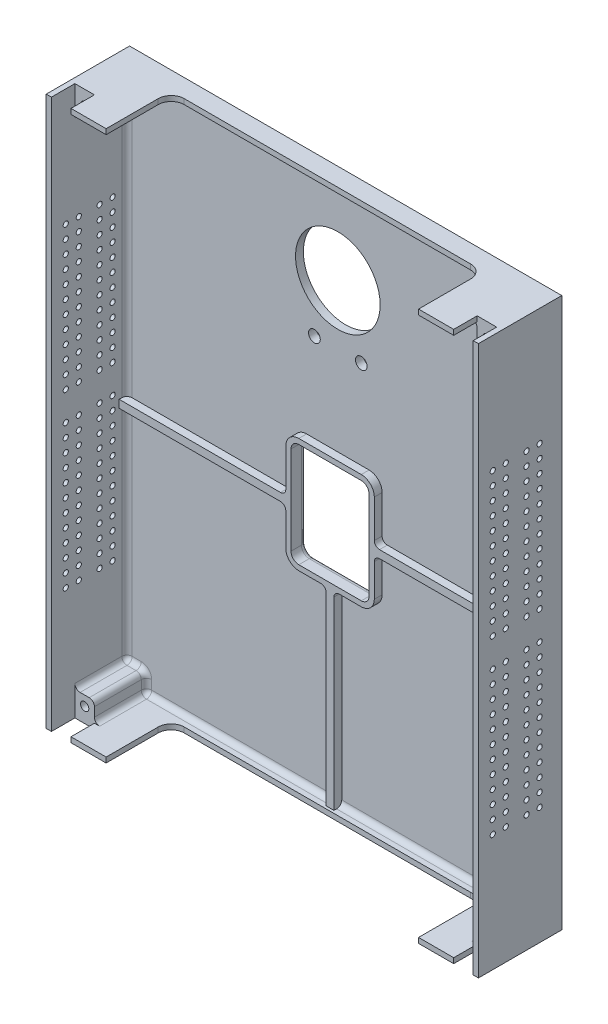
SolidWorks part; units mm, degrees
ref_plane "Front Plane" through (0, 0, 0) normal (0, 0, 1) x (1, 0, 0)
ref_plane "Top Plane" through (0, 0, 0) normal (0, 1, 0) x (1, 0, 0)
ref_plane "Right Plane" through (0, 0, 0) normal (1, 0, 0) x (0, 0, -1)
ref_plane "Plane1" through (0, 0, -1) normal (0, 0, 1) x (1, 0, 0)
sketch "Sketch5" plane through (0, 0, -1) normal (0, 0, 1) x (1, 0, 0)
  line L0 (100, 83.2573) -> (100, -169.2647) construction
  line L2 (17, 83.2573) -> (17, -127.7573)
  line L3 (17, -127.7573) -> (183, -127.7573)
  line L4 (183, 83.2573) -> (183, -127.7573)
  line L5 (17, 83.2573) -> (183, 83.2573)
  circle A0 centre (100, 48.2573) radius 16.25
  point P17 (45, 83.2573)
  dimension "D1" = 166
  dimension "D2" = 83
extrude "Boss-Extrude5" add sketch "Sketch5" along normal blind 3
sketch "Sketch6" plane through (0, 0, 2) normal (0, 0, 1) x (1, 0, 0)
  line L0 (116.25, 48.2573) -> (83.75, 48.2573) construction
  line L2 (86, 35.0451) -> (86, 18.2573)
  line L3 (86, 18.2573) -> (114, 18.2573)
  line L4 (114, 35.0451) -> (114, 18.2573)
  line L5 (100, 48.2573) -> (100, 52.872) construction
  circle A1 centre (100, 48.2573) radius 16.25
  arc A2 (114, 35.0451) -> (86, 35.0451) centre (100, 48.2573) ccw
  circle A6 centre (100, 48.2573) radius 16.25 construction
extrude "Boss-Extrude6" add sketch "Sketch6" along normal blind 3
sketch "Sketch7" plane through (0, 0, 5) normal (0, 0, 1) x (1, 0, 0)
  line L0 (112.75, 33.8351) -> (112.75, 48.2573)
  line L2 (87.25, 48.2573) -> (87.25, 33.8351)
  line L3 (100, 64.5073) -> (100, 48.2573) construction
  line L4 (100, 48.2573) -> (116.25, 48.2573) construction
  arc A8 (112.75, 33.8351) -> (87.25, 33.8351) centre (100, 48.2573) ccw
  circle A9 centre (100, 48.2573) radius 19.25 construction
  circle A10 centre (100, 48.2573) radius 16.25 construction
  circle A12 centre (100, 48.2573) radius 12.75
  arc A13 (112.75, 48.2573) -> (87.25, 48.2573) centre (100, 48.2573) ccw
  dimension "D1" = 1
extrude "Boss-Extrude7" add sketch "Sketch7" along normal blind 4
sketch "Sketch8" plane through (0, 0, 2) normal (0, 0, 1) x (1, 0, 0)
  line L4 (17, -127.7573) -> (183, -127.7573)
  line L5 (183, -127.7573) -> (183, 83.2573)
  line L6 (183, 83.2573) -> (17, 83.2573)
  line L7 (17, 83.2573) -> (17, -127.7573)
  line L8 (17, -127.7573) -> (183, -127.7573)
  line L9 (183, -127.7573) -> (183, 83.2573)
  line L10 (183, 83.2573) -> (17, 83.2573)
  line L11 (17, 83.2573) -> (17, -127.7573)
  line L12 (19, -125.7573) -> (181, -125.7573)
  line L13 (181, -125.7573) -> (181, 81.2573)
  line L14 (181, 81.2573) -> (19, 81.2573)
  line L15 (19, 81.2573) -> (19, -125.7573)
  dimension "D1" = 0
  dimension "D2" = 2
extrude "Boss-Extrude8" add sketch "Sketch8" along normal blind 29
fillet "Fillet2" radius 3 4 edges at (114, 18.2573, 3.5) (114, 35.0451, 3.5) (86, 18.2573, 3.5) (86, 35.0451, 3.5)
sketch "Sketch12" plane through (183, 0, 0) normal (1, 0, 0) x (0, 0, -1)
  circle A0 centre (-12.5, -16.7427) radius 1
  circle A1 centre (-7.5, -16.7427) radius 1
  circle A2 centre (-7.5, -11.7427) radius 1
  circle A3 centre (-7.5, -6.7427) radius 1
  circle A4 centre (-7.5, -1.7427) radius 1
  circle A5 centre (-7.5, 3.2573) radius 1
  circle A6 centre (-7.5, 8.2573) radius 1
  circle A7 centre (-7.5, 13.2573) radius 1
  circle A8 centre (-7.5, 18.2573) radius 1
  circle A9 centre (-7.5, 23.2573) radius 1
  circle A10 centre (-7.5, 28.2573) radius 1
  circle A11 centre (-7.5, 33.2573) radius 1
  circle A12 centre (-7.5, 38.2573) radius 1
  circle A13 centre (-12.5, -11.7427) radius 1
  circle A14 centre (-12.5, -6.7427) radius 1
  circle A15 centre (-12.5, -1.7427) radius 1
  circle A16 centre (-12.5, 3.2573) radius 1
  circle A17 centre (-12.5, 8.2573) radius 1
  circle A18 centre (-12.5, 13.2573) radius 1
  circle A19 centre (-12.5, 18.2573) radius 1
  circle A20 centre (-12.5, 23.2573) radius 1
  circle A21 centre (-12.5, 28.2573) radius 1
  circle A22 centre (-12.5, 33.2573) radius 1
  circle A23 centre (-12.5, 38.2573) radius 1
  circle A24 centre (-12.5, -82.7573) radius 1
  circle A25 centre (-12.5, -77.7573) radius 1
  circle A26 centre (-12.5, -72.7573) radius 1
  circle A27 centre (-12.5, -67.7573) radius 1
  circle A28 centre (-12.5, -62.7573) radius 1
  circle A29 centre (-12.5, -57.7573) radius 1
  circle A30 centre (-12.5, -52.7573) radius 1
  circle A31 centre (-12.5, -47.7573) radius 1
  circle A32 centre (-12.5, -42.7573) radius 1
  circle A33 centre (-12.5, -37.7573) radius 1
  circle A34 centre (-12.5, -32.7573) radius 1
  circle A35 centre (-7.5, -82.7573) radius 1
  circle A36 centre (-7.5, -77.7573) radius 1
  circle A37 centre (-7.5, -72.7573) radius 1
  circle A38 centre (-7.5, -67.7573) radius 1
  circle A39 centre (-7.5, -62.7573) radius 1
  circle A40 centre (-7.5, -57.7573) radius 1
  circle A41 centre (-7.5, -52.7573) radius 1
  circle A42 centre (-7.5, -47.7573) radius 1
  circle A43 centre (-7.5, -42.7573) radius 1
  circle A44 centre (-7.5, -37.7573) radius 1
  circle A45 centre (-7.5, -32.7573) radius 1
  circle A46 centre (-7.5, -27.7573) radius 1
  circle A47 centre (-12.5, -27.7573) radius 1
  circle A48 centre (-20.5, -27.7573) radius 1
  circle A49 centre (-25.5, -27.7573) radius 1
  circle A50 centre (-25.5, -32.7573) radius 1
  circle A51 centre (-25.5, -37.7573) radius 1
  circle A52 centre (-25.5, -42.7573) radius 1
  circle A53 centre (-25.5, -47.7573) radius 1
  circle A54 centre (-25.5, -52.7573) radius 1
  circle A55 centre (-25.5, -57.7573) radius 1
  circle A56 centre (-25.5, -62.7573) radius 1
  circle A57 centre (-25.5, -67.7573) radius 1
  circle A58 centre (-25.5, -72.7573) radius 1
  circle A59 centre (-25.5, -77.7573) radius 1
  circle A60 centre (-25.5, -82.7573) radius 1
  circle A61 centre (-20.5, -32.7573) radius 1
  circle A62 centre (-20.5, -37.7573) radius 1
  circle A63 centre (-20.5, -42.7573) radius 1
  circle A64 centre (-20.5, -47.7573) radius 1
  circle A65 centre (-20.5, -52.7573) radius 1
  circle A66 centre (-20.5, -57.7573) radius 1
  circle A67 centre (-20.5, -62.7573) radius 1
  circle A68 centre (-20.5, -67.7573) radius 1
  circle A69 centre (-20.5, -72.7573) radius 1
  circle A70 centre (-20.5, -77.7573) radius 1
  circle A71 centre (-20.5, -82.7573) radius 1
  circle A72 centre (-20.5, 38.2573) radius 1
  circle A73 centre (-20.5, 33.2573) radius 1
  circle A74 centre (-20.5, 28.2573) radius 1
  circle A75 centre (-20.5, 23.2573) radius 1
  circle A76 centre (-20.5, 18.2573) radius 1
  circle A77 centre (-20.5, 13.2573) radius 1
  circle A78 centre (-20.5, 8.2573) radius 1
  circle A79 centre (-20.5, 3.2573) radius 1
  circle A80 centre (-20.5, -1.7427) radius 1
  circle A81 centre (-20.5, -6.7427) radius 1
  circle A82 centre (-20.5, -11.7427) radius 1
  circle A83 centre (-25.5, 38.2573) radius 1
  circle A84 centre (-25.5, 33.2573) radius 1
  circle A85 centre (-25.5, 28.2573) radius 1
  circle A86 centre (-25.5, 23.2573) radius 1
  circle A87 centre (-25.5, 18.2573) radius 1
  circle A88 centre (-25.5, 13.2573) radius 1
  circle A89 centre (-25.5, 8.2573) radius 1
  circle A90 centre (-25.5, 3.2573) radius 1
  circle A91 centre (-25.5, -1.7427) radius 1
  circle A92 centre (-25.5, -6.7427) radius 1
  circle A93 centre (-25.5, -11.7427) radius 1
  circle A94 centre (-25.5, -16.7427) radius 1
  circle A95 centre (-20.5, -16.7427) radius 1
  dimension "D1" = 2
  dimension "D2" = 12
extrude "Cut-Extrude4" cut sketch "Sketch12" against normal up to surface (2 mm away) up to face at (181, -22.25, 16.5)
sketch "Sketch13" plane through (0, 0, -1) normal (0, 0, -1) x (-1, 0, 0)
  line L0 (-183, -30.7808) -> (-100, -30.7808) construction
  line L1 (-183, -127.7573) -> (-183, 83.2573) construction
  line L6 (-100, 83.2573) -> (-100, -30.7808) construction
  line L7 (-183, 83.2573) -> (-17, 83.2573) construction
  line L14 (-85, -47.7808) -> (-85, -13.7808)
  line L15 (-88, -10.7808) -> (-112, -10.7808)
  line L16 (-115, -13.7808) -> (-115, -47.7808)
  line L17 (-112, -50.7808) -> (-88, -50.7808)
  circle A1 centre (-100, -30.7808) radius 9 construction
  arc A15 (-88, -50.7808) -> (-85, -47.7808) centre (-88, -47.7808) ccw
  arc A16 (-85, -13.7808) -> (-88, -10.7808) centre (-88, -13.7808) ccw
  arc A17 (-112, -10.7808) -> (-115, -13.7808) centre (-112, -13.7808) ccw
  arc A18 (-115, -47.7808) -> (-112, -50.7808) centre (-112, -47.7808) ccw
extrude "Cut-Extrude5" cut sketch "Sketch13" against normal blind 3
sketch "Sketch14" plane through (17, 0, 0) normal (-1, 0, 0) x (0, 0, 1)
  circle A1 centre (12.5, -82.7573) radius 1
  circle A2 centre (12.5, -82.7573) radius 1
  circle A3 centre (12.5, -16.7427) radius 1
  circle A4 centre (12.5, -16.7427) radius 1
  circle A5 centre (7.5, 18.2573) radius 1
  circle A6 centre (7.5, 18.2573) radius 1
  circle A7 centre (7.5, 13.2573) radius 1
  circle A8 centre (7.5, 13.2573) radius 1
  circle A9 centre (7.5, 8.2573) radius 1
  circle A10 centre (7.5, 8.2573) radius 1
  circle A11 centre (7.5, 3.2573) radius 1
  circle A12 centre (7.5, 3.2573) radius 1
  circle A13 centre (7.5, -1.7427) radius 1
  circle A14 centre (7.5, -1.7427) radius 1
  circle A15 centre (7.5, -6.7427) radius 1
  circle A16 centre (7.5, -6.7427) radius 1
  circle A17 centre (7.5, -11.7427) radius 1
  circle A18 centre (7.5, -11.7427) radius 1
  circle A19 centre (7.5, -16.7427) radius 1
  circle A20 centre (7.5, -16.7427) radius 1
  circle A21 centre (12.5, 3.2573) radius 1
  circle A22 centre (12.5, 3.2573) radius 1
  circle A23 centre (12.5, -1.7427) radius 1
  circle A24 centre (12.5, -1.7427) radius 1
  circle A25 centre (12.5, -6.7427) radius 1
  circle A26 centre (12.5, -6.7427) radius 1
  circle A27 centre (12.5, -11.7427) radius 1
  circle A28 centre (12.5, -11.7427) radius 1
  circle A29 centre (7.5, 38.2573) radius 1
  circle A30 centre (7.5, 38.2573) radius 1
  circle A31 centre (7.5, 33.2573) radius 1
  circle A32 centre (7.5, 33.2573) radius 1
  circle A33 centre (7.5, 28.2573) radius 1
  circle A34 centre (7.5, 28.2573) radius 1
  circle A35 centre (7.5, 23.2573) radius 1
  circle A36 centre (7.5, 23.2573) radius 1
  circle A37 centre (12.5, -77.7573) radius 1
  circle A38 centre (12.5, -77.7573) radius 1
  circle A39 centre (12.5, 38.2573) radius 1
  circle A40 centre (12.5, 38.2573) radius 1
  circle A41 centre (12.5, 33.2573) radius 1
  circle A42 centre (12.5, 33.2573) radius 1
  circle A43 centre (12.5, 28.2573) radius 1
  circle A44 centre (12.5, 28.2573) radius 1
  circle A45 centre (12.5, 23.2573) radius 1
  circle A46 centre (12.5, 23.2573) radius 1
  circle A47 centre (12.5, 18.2573) radius 1
  circle A48 centre (12.5, 18.2573) radius 1
  circle A49 centre (12.5, 13.2573) radius 1
  circle A50 centre (12.5, 13.2573) radius 1
  circle A51 centre (12.5, 8.2573) radius 1
  circle A52 centre (12.5, 8.2573) radius 1
  circle A53 centre (12.5, -37.7573) radius 1
  circle A54 centre (12.5, -37.7573) radius 1
  circle A55 centre (12.5, -42.7573) radius 1
  circle A56 centre (12.5, -42.7573) radius 1
  circle A57 centre (12.5, -47.7573) radius 1
  circle A58 centre (12.5, -47.7573) radius 1
  circle A59 centre (12.5, -52.7573) radius 1
  circle A60 centre (12.5, -52.7573) radius 1
  circle A61 centre (12.5, -57.7573) radius 1
  circle A62 centre (12.5, -57.7573) radius 1
  circle A63 centre (12.5, -62.7573) radius 1
  circle A64 centre (12.5, -62.7573) radius 1
  circle A65 centre (12.5, -67.7573) radius 1
  circle A66 centre (12.5, -67.7573) radius 1
  circle A67 centre (12.5, -72.7573) radius 1
  circle A68 centre (12.5, -72.7573) radius 1
  circle A69 centre (7.5, -52.7573) radius 1
  circle A70 centre (7.5, -52.7573) radius 1
  circle A71 centre (7.5, -57.7573) radius 1
  circle A72 centre (7.5, -57.7573) radius 1
  circle A73 centre (7.5, -62.7573) radius 1
  circle A74 centre (7.5, -62.7573) radius 1
  circle A75 centre (7.5, -67.7573) radius 1
  circle A76 centre (7.5, -67.7573) radius 1
  circle A77 centre (7.5, -72.7573) radius 1
  circle A78 centre (7.5, -72.7573) radius 1
  circle A79 centre (7.5, -77.7573) radius 1
  circle A80 centre (7.5, -77.7573) radius 1
  circle A81 centre (7.5, -82.7573) radius 1
  circle A82 centre (7.5, -82.7573) radius 1
  circle A83 centre (12.5, -32.7573) radius 1
  circle A84 centre (12.5, -32.7573) radius 1
  circle A85 centre (25.5, -27.7573) radius 1
  circle A86 centre (25.5, -27.7573) radius 1
  circle A87 centre (20.5, -27.7573) radius 1
  circle A88 centre (20.5, -27.7573) radius 1
  circle A89 centre (12.5, -27.7573) radius 1
  circle A90 centre (12.5, -27.7573) radius 1
  circle A91 centre (7.5, -27.7573) radius 1
  circle A92 centre (7.5, -27.7573) radius 1
  circle A93 centre (7.5, -32.7573) radius 1
  circle A94 centre (7.5, -32.7573) radius 1
  circle A95 centre (7.5, -37.7573) radius 1
  circle A96 centre (7.5, -37.7573) radius 1
  circle A97 centre (7.5, -42.7573) radius 1
  circle A98 centre (7.5, -42.7573) radius 1
  circle A99 centre (7.5, -47.7573) radius 1
  circle A100 centre (7.5, -47.7573) radius 1
  circle A101 centre (25.5, -67.7573) radius 1
  circle A102 centre (25.5, -67.7573) radius 1
  circle A103 centre (25.5, -62.7573) radius 1
  circle A104 centre (25.5, -62.7573) radius 1
  circle A105 centre (25.5, -57.7573) radius 1
  circle A106 centre (25.5, -57.7573) radius 1
  circle A107 centre (25.5, -52.7573) radius 1
  circle A108 centre (25.5, -52.7573) radius 1
  circle A109 centre (25.5, -47.7573) radius 1
  circle A110 centre (25.5, -47.7573) radius 1
  circle A111 centre (25.5, -42.7573) radius 1
  circle A112 centre (25.5, -42.7573) radius 1
  circle A113 centre (25.5, -37.7573) radius 1
  circle A114 centre (25.5, -37.7573) radius 1
  circle A115 centre (25.5, -32.7573) radius 1
  circle A116 centre (25.5, -32.7573) radius 1
  circle A117 centre (20.5, -52.7573) radius 1
  circle A118 centre (20.5, -52.7573) radius 1
  circle A119 centre (20.5, -47.7573) radius 1
  circle A120 centre (20.5, -47.7573) radius 1
  circle A121 centre (20.5, -42.7573) radius 1
  circle A122 centre (20.5, -42.7573) radius 1
  circle A123 centre (20.5, -37.7573) radius 1
  circle A124 centre (20.5, -37.7573) radius 1
  circle A125 centre (20.5, -32.7573) radius 1
  circle A126 centre (20.5, -32.7573) radius 1
  circle A127 centre (25.5, -82.7573) radius 1
  circle A128 centre (25.5, -82.7573) radius 1
  circle A129 centre (25.5, -77.7573) radius 1
  circle A130 centre (25.5, -77.7573) radius 1
  circle A131 centre (25.5, -72.7573) radius 1
  circle A132 centre (25.5, -72.7573) radius 1
  circle A133 centre (20.5, 33.2573) radius 1
  circle A134 centre (20.5, 33.2573) radius 1
  circle A135 centre (20.5, 38.2573) radius 1
  circle A136 centre (20.5, 38.2573) radius 1
  circle A137 centre (20.5, -82.7573) radius 1
  circle A138 centre (20.5, -82.7573) radius 1
  circle A139 centre (20.5, -77.7573) radius 1
  circle A140 centre (20.5, -77.7573) radius 1
  circle A141 centre (20.5, -72.7573) radius 1
  circle A142 centre (20.5, -72.7573) radius 1
  circle A143 centre (20.5, -67.7573) radius 1
  circle A144 centre (20.5, -67.7573) radius 1
  circle A145 centre (20.5, -62.7573) radius 1
  circle A146 centre (20.5, -62.7573) radius 1
  circle A147 centre (20.5, -57.7573) radius 1
  circle A148 centre (20.5, -57.7573) radius 1
  circle A149 centre (20.5, -6.7427) radius 1
  circle A150 centre (20.5, -6.7427) radius 1
  circle A151 centre (20.5, -1.7427) radius 1
  circle A152 centre (20.5, -1.7427) radius 1
  circle A153 centre (20.5, 3.2573) radius 1
  circle A154 centre (20.5, 3.2573) radius 1
  circle A155 centre (20.5, 8.2573) radius 1
  circle A156 centre (20.5, 8.2573) radius 1
  circle A157 centre (20.5, 13.2573) radius 1
  circle A158 centre (20.5, 13.2573) radius 1
  circle A159 centre (20.5, 18.2573) radius 1
  circle A160 centre (20.5, 18.2573) radius 1
  circle A161 centre (20.5, 23.2573) radius 1
  circle A162 centre (20.5, 23.2573) radius 1
  circle A163 centre (20.5, 28.2573) radius 1
  circle A164 centre (20.5, 28.2573) radius 1
  circle A165 centre (25.5, 8.2573) radius 1
  circle A166 centre (25.5, 8.2573) radius 1
  circle A167 centre (25.5, 13.2573) radius 1
  circle A168 centre (25.5, 13.2573) radius 1
  circle A169 centre (25.5, 18.2573) radius 1
  circle A170 centre (25.5, 18.2573) radius 1
  circle A171 centre (25.5, 23.2573) radius 1
  circle A172 centre (25.5, 23.2573) radius 1
  circle A173 centre (25.5, 28.2573) radius 1
  circle A174 centre (25.5, 28.2573) radius 1
  circle A175 centre (25.5, 33.2573) radius 1
  circle A176 centre (25.5, 33.2573) radius 1
  circle A177 centre (25.5, 38.2573) radius 1
  circle A178 centre (25.5, 38.2573) radius 1
  circle A179 centre (20.5, -11.7427) radius 1
  circle A180 centre (20.5, -11.7427) radius 1
  circle A181 centre (20.5, -16.7427) radius 1
  circle A182 centre (20.5, -16.7427) radius 1
  circle A183 centre (25.5, -16.7427) radius 1
  circle A184 centre (25.5, -16.7427) radius 1
  circle A185 centre (25.5, -11.7427) radius 1
  circle A186 centre (25.5, -11.7427) radius 1
  circle A187 centre (25.5, -6.7427) radius 1
  circle A188 centre (25.5, -6.7427) radius 1
  circle A189 centre (25.5, -1.7427) radius 1
  circle A190 centre (25.5, -1.7427) radius 1
  circle A191 centre (25.5, 3.2573) radius 1
  circle A192 centre (25.5, 3.2573) radius 1
  dimension "D1" = 0
  dimension "D2" = 0
  dimension "D3" = 0
  dimension "D4" = 0
  dimension "D5" = 0
  dimension "D6" = 0
  dimension "D7" = 0
  dimension "D8" = 0
  dimension "D9" = 0
  dimension "D10" = 0
  dimension "D11" = 0
  dimension "D12" = 0
  dimension "D13" = 0
  dimension "D14" = 0
  dimension "D15" = 0
  dimension "D16" = 0
  dimension "D17" = 0
  dimension "D18" = 0
  dimension "D19" = 0
  dimension "D20" = 0
  dimension "D21" = 0
  dimension "D22" = 0
  dimension "D23" = 0
  dimension "D24" = 0
  dimension "D25" = 0
  dimension "D26" = 0
  dimension "D27" = 0
  dimension "D28" = 0
  dimension "D29" = 0
  dimension "D30" = 0
  dimension "D31" = 0
  dimension "D32" = 0
  dimension "D33" = 0
  dimension "D34" = 0
  dimension "D35" = 0
  dimension "D36" = 0
  dimension "D37" = 0
  dimension "D38" = 0
  dimension "D39" = 0
  dimension "D40" = 0
  dimension "D41" = 0
  dimension "D42" = 0
  dimension "D43" = 0
  dimension "D44" = 0
  dimension "D45" = 0
  dimension "D46" = 0
  dimension "D47" = 0
  dimension "D48" = 0
  dimension "D49" = 0
  dimension "D50" = 0
  dimension "D51" = 0
  dimension "D52" = 0
  dimension "D53" = 0
  dimension "D54" = 0
  dimension "D55" = 0
  dimension "D56" = 0
  dimension "D57" = 0
  dimension "D58" = 0
  dimension "D59" = 0
  dimension "D60" = 0
  dimension "D61" = 0
  dimension "D62" = 0
  dimension "D63" = 0
  dimension "D64" = 0
  dimension "D65" = 0
  dimension "D66" = 0
  dimension "D67" = 0
  dimension "D68" = 0
  dimension "D69" = 0
  dimension "D70" = 0
  dimension "D71" = 0
  dimension "D72" = 0
  dimension "D73" = 0
  dimension "D74" = 0
  dimension "D75" = 0
  dimension "D76" = 0
  dimension "D77" = 0
  dimension "D78" = 0
  dimension "D79" = 0
  dimension "D80" = 0
  dimension "D81" = 0
  dimension "D82" = 0
  dimension "D83" = 0
  dimension "D84" = 0
  dimension "D85" = 0
  dimension "D86" = 0
  dimension "D87" = 0
  dimension "D88" = 0
  dimension "D89" = 0
  dimension "D90" = 0
  dimension "D91" = 0
  dimension "D92" = 0
  dimension "D93" = 0
  dimension "D94" = 0
  dimension "D95" = 0
  dimension "D96" = 0
extrude "Cut-Extrude6" cut sketch "Sketch14" against normal up to surface (2 mm away) up to face at (19, -22.25, 16.5)
sketch "Sketch15" plane through (0, -127.7573, 0) normal (0, -1, 0) x (1, 0, 0)
  line L5 (100, -1) -> (100, 31) construction
  line L6 (17, -1) -> (183, -1) construction
  line L7 (17, 31) -> (183, 31) construction
  line L8 (40, 31) -> (160, 31)
  line L9 (40, 31) -> (40, 11)
  line L10 (45, 6) -> (155, 6)
  line L11 (160, 31) -> (160, 11)
  arc A4 (155, 6) -> (160, 11) centre (155, 11) ccw
  arc A5 (40, 11) -> (45, 6) centre (45, 11) ccw
  point P12 (160, 6)
  point P15 (40, 6)
  dimension "D4" = 5
  dimension "D1" = 60
  dimension "D2" = 120
  dimension "D3" = 25
extrude "Cut-Extrude7" cut sketch "Sketch15" against normal up to surface (2 mm away) up to face at (100, -125.7573, 16.5)
sketch "Sketch16" plane through (0, 83.2573, 0) normal (0, 1, 0) x (1, 0, 0)
  line L4 (40, -31) -> (160, -31)
  line L5 (40, -31) -> (160, -31)
  line L6 (160, -31) -> (160, -11)
  line L7 (160, -31) -> (160, -11)
  line L12 (155, -6) -> (45, -6)
  line L13 (155, -6) -> (45, -6)
  line L14 (40, -11) -> (40, -31)
  line L15 (40, -11) -> (40, -31)
  arc A2 (160, -11) -> (155, -6) centre (155, -11) ccw
  arc A3 (160, -11) -> (155, -6) centre (155, -11) ccw
  arc A4 (45, -6) -> (40, -11) centre (45, -11) ccw
  arc A5 (45, -6) -> (40, -11) centre (45, -11) ccw
  dimension "D1" = 0
extrude "Cut-Extrude8" cut sketch "Sketch16" against normal up to surface (2 mm away) up to face at (100, 81.2573, 16.5)
sketch "Sketch18" plane through (0, 0, 2) normal (0, 0, 1) x (1, 0, 0)
  line L1 (19, -125.7573) -> (26.5, -125.7573)
  line L2 (19, -125.7573) -> (19, -118.2573)
  line L3 (19, -118.2573) -> (26.5, -118.2573)
  line L4 (26.5, -125.7573) -> (26.5, -118.2573)
  line L5 (181, -125.7573) -> (173.5, -125.7573)
  line L6 (181, -125.7573) -> (181, -118.2573)
  line L7 (181, -118.2573) -> (173.5, -118.2573)
  line L8 (173.5, -125.7573) -> (173.5, -118.2573)
  line L9 (19, 81.2573) -> (26.5, 81.2573)
  line L10 (19, 81.2573) -> (19, 73.7573)
  line L11 (19, 73.7573) -> (26.5, 73.7573)
  line L12 (26.5, 81.2573) -> (26.5, 73.7573)
  line L13 (181, 81.2573) -> (173.5, 81.2573)
  line L14 (181, 81.2573) -> (181, 73.7573)
  line L15 (181, 73.7573) -> (173.5, 73.7573)
  line L16 (173.5, 81.2573) -> (173.5, 73.7573)
extrude "Boss-Extrude10" add sketch "Sketch18" along normal blind 20
fillet "Fillet3" radius 2 12 edges at (181, 73.7573, 12) (173.5, 73.7573, 12) (173.5, 81.2573, 12) (26.5, 81.2573, 12) (26.5, 73.7573, 12) (19, 73.7573, 12) (19, -118.2573, 12) (26.5, -118.2573, 12) (26.5, -125.7573, 12) (181, -118.2573, 12) (173.5, -118.2573, 12) (173.5, -125.7573, 12)
sketch "Sketch19" plane through (0, 0, 22) normal (0, 0, 1) x (1, 0, 0)
  line L4 (100, -127.7573) -> (100, 83.2573) construction
  line L5 (45, -127.7573) -> (155, -127.7573) construction
  line L6 (155, 83.2573) -> (45, 83.2573) construction
  line L7 (100, -22.25) -> (17, -22.25) construction
  line L8 (17, 83.2573) -> (17, -127.7573) construction
  circle A0 centre (22.75, -122.0073) radius 1.6
  circle A1 centre (177.25, -122.0073) radius 1.6
  circle A2 centre (177.25, 77.5073) radius 1.6
  circle A3 centre (22.75, 77.5073) radius 1.6
extrude "Cut-Extrude9" cut sketch "Sketch19" against normal up to surface (23 mm away) up to face at (100, -30.7808, -1)
fillet "Fillet4" radius 2 24 edges at (180.4142, -117.6715, 2) (177.25, -118.2573, 2) (174.0858, -118.8431, 2) (173.5, -122.0073, 2) (172.9142, -125.1715, 2) (100, -125.7573, 2) (27.0858, -125.1715, 2) (26.5, -122.0073, 2) (25.9142, -118.8431, 2) (22.75, -118.2573, 2) (19.5858, -117.6715, 2) (19, -22.25, 2) (19.5858, 73.1715, 2) (22.75, 73.7573, 2) (25.9142, 74.3431, 2) (26.5, 77.5073, 2) (27.0858, 80.6715, 2) (100, 81.2573, 2) (172.9142, 80.6715, 2) (173.5, 77.5073, 2) (174.0858, 74.3431, 2) (177.25, 73.7573, 2) (180.4142, 73.1715, 2) (181, -22.25, 2)
sketch "Sketch20" plane through (0, 0, 2) normal (0, 0, 1) x (1, 0, 0)
  line L0 (83, -30.2573) -> (83, -13.7808)
  line L1 (155, 83.2573) -> (45, 83.2573) construction
  line L2 (45, -127.7573) -> (155, -127.7573) construction
  line L3 (88, -10.7808) -> (112, -10.7808) construction
  line L4 (101.5, -127.7573) -> (98.5, -127.7573)
  line L5 (101.5, -127.7573) -> (101.5, -52.7808)
  line L6 (101.5, 83.2573) -> (98.5, 83.2573)
  line L7 (98.5, -127.7573) -> (98.5, -52.7808)
  line L8 (115, -13.7808) -> (115, -47.7808) construction
  line L9 (112, -50.7808) -> (88, -50.7808) construction
  line L10 (85, -47.7808) -> (85, -13.7808) construction
  line L11 (88, -10.7808) -> (112, -10.7808)
  line L12 (115, -13.7808) -> (115, -47.7808)
  line L13 (112, -50.7808) -> (88, -50.7808)
  line L14 (85, -47.7808) -> (85, -13.7808)
  line L15 (88, -8.7808) -> (112, -8.7808)
  line L16 (117, -13.7808) -> (117, -30.2573)
  line L17 (112, -52.7808) -> (101.5, -52.7808)
  line L18 (83, -47.7808) -> (83, -33.2573)
  line L20 (183, -127.7573) -> (183, 83.2573) construction
  line L21 (183, -33.2573) -> (117, -33.2573)
  line L22 (183, -33.2573) -> (183, -30.2573)
  line L23 (183, -30.2573) -> (117, -30.2573)
  line L24 (17, -33.2573) -> (17, -30.2573)
  line L25 (17, 83.2573) -> (17, -127.7573) construction
  line L26 (83, -33.2573) -> (17, -33.2573)
  line L28 (98.5, -52.7808) -> (88, -52.7808)
  line L31 (83, -30.2573) -> (17, -30.2573)
  line L33 (112, -52.7808) -> (88, -52.7808) construction
  line L35 (117, -33.2573) -> (117, -47.7808)
  line L38 (117, -13.7808) -> (117, -47.7808) construction
  line L39 (88, -8.7808) -> (112, -8.7808) construction
  line L40 (83, -47.7808) -> (83, -13.7808) construction
  line L44 (98.5, 64.4379) -> (98.5, 83.2573)
  line L45 (101.5, 64.4379) -> (101.5, 83.2573)
  line L49 (112.75, 48.2573) -> (112.75, 38.1826)
  line L51 (87.25, 38.1826) -> (87.25, 48.2573)
  arc A0 (88, -10.7808) -> (85, -13.7808) centre (88, -13.7808) ccw construction
  arc A1 (115, -13.7808) -> (112, -10.7808) centre (112, -13.7808) ccw construction
  arc A2 (112, -50.7808) -> (115, -47.7808) centre (112, -47.7808) ccw construction
  arc A3 (85, -47.7808) -> (88, -50.7808) centre (88, -47.7808) ccw construction
  arc A4 (88, -10.7808) -> (85, -13.7808) centre (88, -13.7808) ccw
  arc A5 (115, -13.7808) -> (112, -10.7808) centre (112, -13.7808) ccw
  arc A6 (112, -50.7808) -> (115, -47.7808) centre (112, -47.7808) ccw
  arc A7 (85, -47.7808) -> (88, -50.7808) centre (88, -47.7808) ccw
  arc A8 (117, -13.7808) -> (112, -8.7808) centre (112, -13.7808) ccw
  arc A9 (112, -52.7808) -> (117, -47.7808) centre (112, -47.7808) ccw
  arc A10 (83, -47.7808) -> (88, -52.7808) centre (88, -47.7808) ccw
  arc A11 (88, -8.7808) -> (83, -13.7808) centre (88, -13.7808) ccw
  arc A14 (112.75, 48.2573) -> (87.25, 48.2573) centre (100, 48.2573) ccw
  arc A15 (112.75, 38.1826) -> (87.25, 38.1826) centre (100, 48.2573) ccw
  arc A18 (101.5, 64.4379) -> (98.5, 64.4379) centre (100, 48.2573) ccw
  dimension "D1" = 0
  dimension "D3" = 2
extrude "Boss-Extrude11" add sketch "Sketch20" along normal blind 3
fillet "Fillet5" radius 2 8 edges at (98.5, -52.7808, 3.5) (101.5, -52.7808, 3.5) (117, -33.2573, 3.5) (117, -30.2573, 3.5) (83, -33.2573, 3.5) (83, -30.2573, 3.5) (101.5, 67.4488, 3.5) (98.5, 67.4488, 3.5)
sketch "Sketch21" plane through (0, 0, -1) normal (0, 0, -1) x (-1, 0, 0)
  circle A0 centre (-109, 25.2573) radius 2.25
  circle A1 centre (-91, 25.2573) radius 2.25
extrude "Cut-Extrude10" cut sketch "Sketch21" against normal blind 3
fillet "Fillet6" radius 2 8 edges at (85.8787, -49.9021, -1) (100, -50.7808, -1) (114.1213, -49.9021, -1) (115, -30.7808, -1) (114.1213, -11.6594, -1) (100, -10.7808, -1) (85.8787, -11.6594, -1) (85, -30.7808, -1)
chamfer "Chamfer1" distance 1.5 angle 45 4 edges at (21.15, 77.5073, -1) (21.15, -122.0073, -1) (175.65, -122.0073, -1) (175.65, 77.5073, -1)
sketch "Sketch22" plane through (0, 0, 31) normal (0, 0, 1) x (1, 0, 0)
  line L0 (173.5, -120.2573) -> (173.5, -123.7573) construction
  line L1 (173.5, -125.7573) -> (173.5, -127.7573)
  line L3 (181, -125.7573) -> (173.5, -125.7573)
  line L4 (160, -127.7573) -> (183, -127.7573) construction
  line L5 (183, -127.7573) -> (183, 83.2573) construction
  line L7 (181, -127.7573) -> (173.5, -127.7573)
  line L8 (100, -127.7573) -> (100, 83.2573) construction
  line L9 (45, -127.7573) -> (155, -127.7573) construction
  line L10 (155, 83.2573) -> (45, 83.2573) construction
  line L11 (183, -22.25) -> (17, -22.25) construction
  line L12 (17, 83.2573) -> (17, -127.7573) construction
  line L13 (19, -127.7573) -> (26.5, -127.7573)
  line L15 (19, -125.7573) -> (26.5, -125.7573)
  line L16 (26.5, -125.7573) -> (26.5, -127.7573)
  line L17 (26.5, 81.2573) -> (26.5, 83.2573)
  line L18 (19, 81.2573) -> (26.5, 81.2573)
  line L20 (19, 83.2573) -> (26.5, 83.2573)
  line L21 (181, 83.2573) -> (173.5, 83.2573)
  line L23 (181, 81.2573) -> (173.5, 81.2573)
  line L24 (173.5, 81.2573) -> (173.5, 83.2573)
  line L25 (19, 83.2573) -> (19, 81.2573)
  line L26 (181, 83.2573) -> (181, 81.2573)
  line L27 (181, -125.7573) -> (181, -127.7573)
  line L28 (19, -125.7573) -> (19, -127.7573)
  dimension "D1" = 2
extrude "Cut-Extrude11" cut sketch "Sketch22" against normal up to surface (9 mm away) up to face at (21.15, 77.5073, 22)
sketch "Sketch25" plane through (98.5, 0, 0) normal (-1, 0, 0) x (0, 0, 1)
  line L4 (2, 79.2573) -> (2, 69.2171)
  line L5 (2, 69.2171) -> (5, 69.2171)
  line L6 (5, 69.2171) -> (5, 81.2573)
  line L7 (5, 81.2573) -> (4, 81.2573)
  line L8 (2, 79.2573) -> (2, 12.2329)
  line L9 (2, 12.2329) -> (11.2434, 12.2329)
  line L10 (11.2434, 12.2329) -> (11.2434, 81.2573)
  line L11 (11.2434, 81.2573) -> (4, 81.2573)
  arc A1 (4, 81.2573) -> (2, 79.2573) centre (4, 79.2573) ccw
  arc A2 (4, 81.2573) -> (2, 79.2573) centre (4, 79.2573) ccw
  point P4 (11.2434, 55.1831)
  point P8 (2, 45.0585)
  point P10 (11.2434, 81.2573)
  point P12 (11.2434, 45.0585)
  point P13 (11.2434, 22.2929)
  point P14 (11.2434, 12.2329)
  point P15 (2, 12.2329)
  dimension "D1" = 0
extrude "Cut-Extrude13" cut sketch "Sketch25" against normal blind 30 and the other way blind 20
